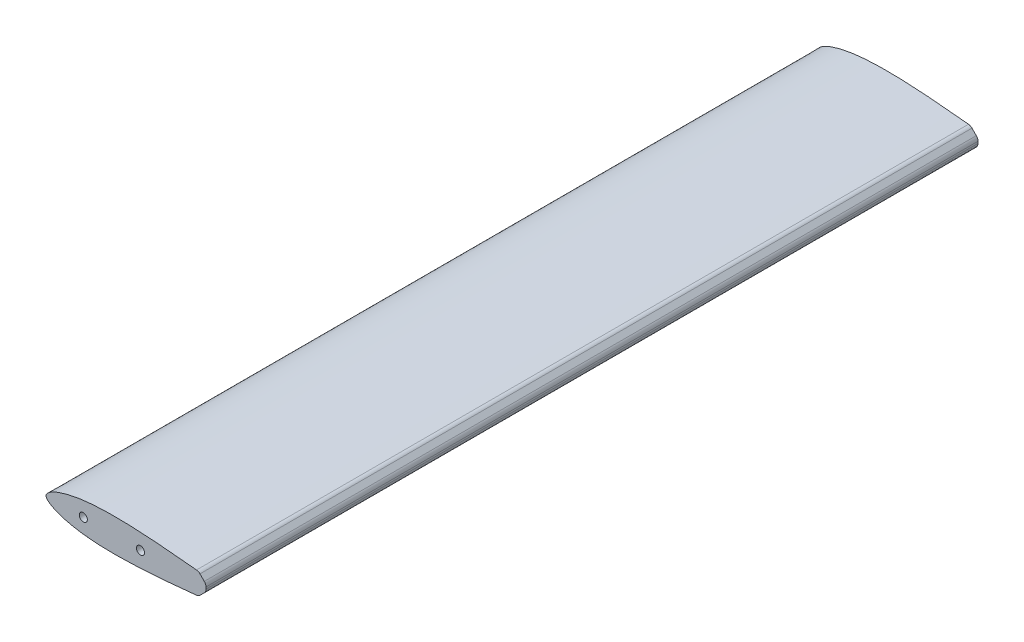
SolidWorks part; units mm, degrees
material "Wing Foam"
ref_plane "Front Plane" through (0, 0, 0) normal (0, 0, 1) x (1, 0, 0)
ref_plane "Top Plane" through (0, 0, 0) normal (0, 1, 0) x (1, 0, 0)
ref_plane "Right Plane" through (0, 0, 0) normal (1, 0, 0) x (0, 0, -1)
curve "Curve2"
  spline degree 3 poles (25.2129, -0.0083, 0) (25.4479, 0, 0) (25.2129, 0.0083, 0) (25.0266, 0.0317, 0) (24.5854, 0.0743, 0) (24.0514, 0.1262, 0) (23.3593, 0.1828, 0) (22.5445, 0.2515, 0) (21.6077, 0.334, 0) (20.5667, 0.4316, 0) (19.4358, 0.5428, 0) (18.232, 0.6656, 0) (16.9723, 0.7976, 0) (15.6739, 0.934, 0) (14.3536, 1.0707, 0) (13.0278, 1.2023, 0) (11.7119, 1.3224, 0) (10.4203, 1.4262, 0) (9.1661, 1.5078, 0) (7.9608, 1.5623, 0) (6.8146, 1.5854, 0) (5.7365, 1.5758, 0) (4.7346, 1.5313, 0) (3.8153, 1.4513, 0) (2.9837, 1.336, 0) (2.2443, 1.1893, 0) (1.6014, 1.0184, 0) (1.0596, 0.829, 0) (0.6236, 0.6287, 0) (0.2959, 0.4198, 0) (0.0819, 0.2242, 0) (-0.0333, 0, 0) (0.0819, -0.2242, 0) (0.2959, -0.4198, 0) (0.6236, -0.6287, 0) (1.0596, -0.829, 0) (1.6014, -1.0184, 0) (2.2443, -1.1893, 0) (2.9837, -1.336, 0) (3.8153, -1.4513, 0) (4.7346, -1.5313, 0) (5.7365, -1.5758, 0) (6.8146, -1.5854, 0) (7.9608, -1.5623, 0) (9.1661, -1.5078, 0) (10.4203, -1.4262, 0) (11.7119, -1.3224, 0) (13.0278, -1.2023, 0) (14.3536, -1.0707, 0) (15.6739, -0.934, 0) (16.9723, -0.7976, 0) (18.232, -0.6656, 0) (19.4358, -0.5428, 0) (20.5667, -0.4316, 0) (21.6077, -0.334, 0) (22.5445, -0.2515, 0) (23.3593, -0.1828, 0) (24.0514, -0.1262, 0) (24.5854, -0.0743, 0) (25.0266, -0.0317, 0) (25.2129, -0.0083, 0) (25.4479, 0, 0) (25.2129, 0.0083, 0) knots -0.014696 -0.00674 -0.001726 0 0.001726 0.00674 0.014696 0.025359 0.038701 0.054619 0.072867 0.093174 0.115236 0.138727 0.163314 0.188652 0.214406 0.240251 0.265875 0.290998 0.315355 0.338723 0.360924 0.381802 0.401202 0.419043 0.435269 0.449839 0.46271 0.473799 0.48306 0.490498 0.496137 0.5 0.503863 0.509502 0.51694 0.526201 0.53729 0.550161 0.564731 0.580957 0.598798 0.618198 0.639076 0.661277 0.684645 0.709002 0.734125 0.759749 0.785594 0.811348 0.836686 0.861273 0.884764 0.906826 0.927133 0.945381 0.961299 0.974641 0.985304 0.99326 0.998274 1 1.001726 1.00674 1.014696 periodic
sketch "Sketch4" plane through (0, 0, 0) normal (0, 0, 1) x (1, 0, 0)
  line L0 (0, 1.7966) -> (0, -1.8631) construction
  line L1 (234.188, 0) -> (0, 0) construction
  spline S2 degree 3 poles (232.4627, -0.0763) (234.6297, 0) (232.4627, 0.0763) (230.7453, 0.2925) (226.6771, 0.6852) (221.7536, 1.164) (215.3729, 1.6852) (207.8606, 2.3193) (199.2232, 3.0796) (189.6249, 3.9791) (179.1985, 5.0042) (168.0995, 6.1368) (156.485, 7.3536) (144.513, 8.6117) (132.34, 9.8717) (120.1165, 11.0852) (107.9836, 12.1928) (96.0751, 13.1495) (84.5114, 13.9023) (73.3989, 14.4043) (62.8304, 14.6175) (52.8907, 14.5289) (43.6527, 14.1188) (35.1769, 13.3807) (27.5098, 12.3176) (20.6924, 10.9653) (14.765, 9.3899) (9.7694, 7.6438) (5.7494, 5.7962) (2.7281, 3.8708) (0.7551, 2.0669) (-0.307, 0) (0.7551, -2.0669) (2.7281, -3.8708) (5.7494, -5.7962) (9.7694, -7.6438) (14.765, -9.3899) (20.6924, -10.9653) (27.5098, -12.3176) (35.1769, -13.3807) (43.6527, -14.1188) (52.8907, -14.5289) (62.8304, -14.6175) (73.3989, -14.4043) (84.5114, -13.9023) (96.0751, -13.1495) (107.9836, -12.1928) (120.1165, -11.0852) (132.34, -9.8717) (144.513, -8.6117) (156.485, -7.3536) (168.0995, -6.1368) (179.1985, -5.0042) (189.6249, -3.9791) (199.2232, -3.0796) (207.8606, -2.3193) (215.3729, -1.6852) (221.7536, -1.164) (226.6771, -0.6852) (230.7453, -0.2925) (232.4627, -0.0763) (234.6297, 0) (232.4627, 0.0763) knots -0.014696 -0.00674 -0.001726 0 0.001726 0.00674 0.014696 0.025359 0.038701 0.054619 0.072867 0.093174 0.115236 0.138727 0.163314 0.188652 0.214406 0.240251 0.265875 0.290998 0.315355 0.338723 0.360924 0.381802 0.401202 0.419043 0.435269 0.449839 0.46271 0.473799 0.48306 0.490498 0.496137 0.5 0.503863 0.509502 0.51694 0.526201 0.53729 0.550161 0.564731 0.580957 0.598798 0.618198 0.639076 0.661277 0.684645 0.709002 0.734125 0.759749 0.785594 0.811348 0.836686 0.861273 0.884764 0.906826 0.927133 0.945381 0.961299 0.974641 0.985304 0.99326 0.998274 1 1.001726 1.00674 1.014696 only from (234.188, 0) to (234.188, 0)
  dimension "D1" = 234.188
extrude "Boss-Extrude1" add sketch "Sketch4" along normal mid plane 685.8
sketch "Sketch5" plane through (0, 0, -342.9) normal (0, 0, -1) x (-1, 0, 0)
  line L0 (0, 0) -> (-230.7877, -0.2744) construction
  circle A0 centre (-33.147, -0.0394) radius 3.6
  circle A1 centre (-83.947, -0.0998) radius 3.6
  spline S0 degree 3 poles (-232.4627, 0.0763) (-234.6297, 0) (-232.4627, -0.0763) (-230.7453, -0.2925) (-226.6771, -0.6852) (-221.7536, -1.164) (-215.3729, -1.6852) (-207.8606, -2.3193) (-199.2232, -3.0796) (-189.6249, -3.9791) (-179.1985, -5.0042) (-168.0995, -6.1368) (-156.485, -7.3536) (-144.513, -8.6117) (-132.34, -9.8717) (-120.1165, -11.0852) (-107.9836, -12.1928) (-96.0751, -13.1495) (-84.5114, -13.9023) (-73.3989, -14.4043) (-62.8304, -14.6175) (-52.8907, -14.5289) (-43.6527, -14.1188) (-35.1769, -13.3807) (-27.5098, -12.3176) (-20.6924, -10.9653) (-14.765, -9.3899) (-9.7694, -7.6438) (-5.7494, -5.7962) (-2.7281, -3.8708) (-0.7551, -2.0669) (0.307, 0) (-0.7551, 2.0669) (-2.7281, 3.8708) (-5.7494, 5.7962) (-9.7694, 7.6438) (-14.765, 9.3899) (-20.6924, 10.9653) (-27.5098, 12.3176) (-35.1769, 13.3807) (-43.6527, 14.1188) (-52.8907, 14.5289) (-62.8304, 14.6175) (-73.3989, 14.4043) (-84.5114, 13.9023) (-96.0751, 13.1495) (-107.9836, 12.1928) (-120.1165, 11.0852) (-132.34, 9.8717) (-144.513, 8.6117) (-156.485, 7.3536) (-168.0995, 6.1368) (-179.1985, 5.0042) (-189.6249, 3.9791) (-199.2232, 3.0796) (-207.8606, 2.3193) (-215.3729, 1.6852) (-221.7536, 1.164) (-226.6771, 0.6852) (-230.7453, 0.2925) (-232.4627, 0.0763) (-234.6297, 0) (-232.4627, -0.0763) knots -0.014696 -0.00674 -0.001726 0 0.001726 0.00674 0.014696 0.025359 0.038701 0.054619 0.072867 0.093174 0.115236 0.138727 0.163314 0.188652 0.214406 0.240251 0.265875 0.290998 0.315355 0.338723 0.360924 0.381802 0.401202 0.419043 0.435269 0.449839 0.46271 0.473799 0.48306 0.490498 0.496137 0.5 0.503863 0.509502 0.51694 0.526201 0.53729 0.550161 0.564731 0.580957 0.598798 0.618198 0.639076 0.661277 0.684645 0.709002 0.734125 0.759749 0.785594 0.811348 0.836686 0.861273 0.884764 0.906826 0.927133 0.945381 0.961299 0.974641 0.985304 0.99326 0.998274 1 1.001726 1.00674 1.014696 only from (-234.188, 0) to (-234.188, 0) construction
  dimension "D1" = 7.2
  dimension "D2" = 33.147
  dimension "D3" = 50.8
extrude "Cut-Extrude1" cut sketch "Sketch5" against normal up to next
sketch "Sketch6" plane through (0, 0, 342.9) normal (0, 0, 1) x (1, 0, 0)
  line L0 (142.113, -8.8584) -> (142.113, 8.8584)
  line L1 (135.485, -9.5426) -> (142.113, -2.9146)
  line L2 (142.113, -2.9146) -> (147.4954, -8.297)
  line L3 (135.5041, 9.5406) -> (142.113, 2.9318)
  line L4 (142.113, 2.9318) -> (147.4798, 8.2986)
  spline S0 degree 3 poles (232.4627, -0.0763) (234.6297, 0) (232.4627, 0.0763) (230.7453, 0.2925) (226.6771, 0.6852) (221.7536, 1.164) (215.3729, 1.6852) (207.8606, 2.3193) (199.2232, 3.0796) (189.6249, 3.9791) (179.1985, 5.0042) (168.0995, 6.1368) (156.485, 7.3536) (144.513, 8.6117) (132.34, 9.8717) (120.1165, 11.0852) (107.9836, 12.1928) (96.0751, 13.1495) (84.5114, 13.9023) (73.3989, 14.4043) (62.8304, 14.6175) (52.8907, 14.5289) (43.6527, 14.1188) (35.1769, 13.3807) (27.5098, 12.3176) (20.6924, 10.9653) (14.765, 9.3899) (9.7694, 7.6438) (5.7494, 5.7962) (2.7281, 3.8708) (0.7551, 2.0669) (-0.307, 0) (0.7551, -2.0669) (2.7281, -3.8708) (5.7494, -5.7962) (9.7694, -7.6438) (14.765, -9.3899) (20.6924, -10.9653) (27.5098, -12.3176) (35.1769, -13.3807) (43.6527, -14.1188) (52.8907, -14.5289) (62.8304, -14.6175) (73.3989, -14.4043) (84.5114, -13.9023) (96.0751, -13.1495) (107.9836, -12.1928) (120.1165, -11.0852) (132.34, -9.8717) (144.513, -8.6117) (156.485, -7.3536) (168.0995, -6.1368) (179.1985, -5.0042) (189.6249, -3.9791) (199.2232, -3.0796) (207.8606, -2.3193) (215.3729, -1.6852) (221.7536, -1.164) (226.6771, -0.6852) (230.7453, -0.2925) (232.4627, -0.0763) (234.6297, 0) (232.4627, 0.0763) knots -0.014696 -0.00674 -0.001726 0 0.001726 0.00674 0.014696 0.025359 0.038701 0.054619 0.072867 0.093174 0.115236 0.138727 0.163314 0.188652 0.214406 0.240251 0.265875 0.290998 0.315355 0.338723 0.360924 0.381802 0.401202 0.419043 0.435269 0.449839 0.46271 0.473799 0.48306 0.490498 0.496137 0.5 0.503863 0.509502 0.51694 0.526201 0.53729 0.550161 0.564731 0.580957 0.598798 0.618198 0.639076 0.661277 0.684645 0.709002 0.734125 0.759749 0.785594 0.811348 0.836686 0.861273 0.884764 0.906826 0.927133 0.945381 0.961299 0.974641 0.985304 0.99326 0.998274 1 1.001726 1.00674 1.014696 only from (234.188, 0) to (234.188, 0) construction
  spline S1 degree 3 poles (232.4627, -0.0763) (234.6297, 0) (232.4627, 0.0763) (230.7453, 0.2925) (226.6771, 0.6852) (221.7536, 1.164) (215.3729, 1.6852) (207.8606, 2.3193) (199.2232, 3.0796) (189.6249, 3.9791) (179.1985, 5.0042) (168.0995, 6.1368) (156.485, 7.3536) (144.513, 8.6117) (132.34, 9.8717) (120.1165, 11.0852) (107.9836, 12.1928) (96.0751, 13.1495) (84.5114, 13.9023) (73.3989, 14.4043) (62.8304, 14.6175) (52.8907, 14.5289) (43.6527, 14.1188) (35.1769, 13.3807) (27.5098, 12.3176) (20.6924, 10.9653) (14.765, 9.3899) (9.7694, 7.6438) (5.7494, 5.7962) (2.7281, 3.8708) (0.7551, 2.0669) (-0.307, 0) (0.7551, -2.0669) (2.7281, -3.8708) (5.7494, -5.7962) (9.7694, -7.6438) (14.765, -9.3899) (20.6924, -10.9653) (27.5098, -12.3176) (35.1769, -13.3807) (43.6527, -14.1188) (52.8907, -14.5289) (62.8304, -14.6175) (73.3989, -14.4043) (84.5114, -13.9023) (96.0751, -13.1495) (107.9836, -12.1928) (120.1165, -11.0852) (132.34, -9.8717) (144.513, -8.6117) (156.485, -7.3536) (168.0995, -6.1368) (179.1985, -5.0042) (189.6249, -3.9791) (199.2232, -3.0796) (207.8606, -2.3193) (215.3729, -1.6852) (221.7536, -1.164) (226.6771, -0.6852) (230.7453, -0.2925) (232.4627, -0.0763) (234.6297, 0) (232.4627, 0.0763) knots -0.014696 -0.00674 -0.001726 0 0.001726 0.00674 0.014696 0.025359 0.038701 0.054619 0.072867 0.093174 0.115236 0.138727 0.163314 0.188652 0.214406 0.240251 0.265875 0.290998 0.315355 0.338723 0.360924 0.381802 0.401202 0.419043 0.435269 0.449839 0.46271 0.473799 0.48306 0.490498 0.496137 0.5 0.503863 0.509502 0.51694 0.526201 0.53729 0.550161 0.564731 0.580957 0.598798 0.618198 0.639076 0.661277 0.684645 0.709002 0.734125 0.759749 0.785594 0.811348 0.836686 0.861273 0.884764 0.906826 0.927133 0.945381 0.961299 0.974641 0.985304 0.99326 0.998274 1 1.001726 1.00674 1.014696 only from (234.188, 0) to (234.188, 0)
  point P3 (234.188, 0)
  spline M9 degree 3 poles (232.4627, -0.0763) (234.6297, 0) (232.4627, 0.0763) (230.7453, 0.2925) (226.6771, 0.6852) (221.7536, 1.164) (215.3729, 1.6852) (207.8606, 2.3193) (199.2232, 3.0796) (189.6249, 3.9791) (179.1985, 5.0042) (168.0995, 6.1368) (156.485, 7.3536) (144.513, 8.6117) (132.34, 9.8717) (120.1165, 11.0852) (107.9836, 12.1928) (96.0751, 13.1495) (84.5114, 13.9023) (73.3989, 14.4043) (62.8304, 14.6175) (52.8907, 14.5289) (43.6527, 14.1188) (35.1769, 13.3807) (27.5098, 12.3176) (20.6924, 10.9653) (14.765, 9.3899) (9.7694, 7.6438) (5.7494, 5.7962) (2.7281, 3.8708) (0.7551, 2.0669) (-0.307, 0) (0.7551, -2.0669) (2.7281, -3.8708) (5.7494, -5.7962) (9.7694, -7.6438) (14.765, -9.3899) (20.6924, -10.9653) (27.5098, -12.3176) (35.1769, -13.3807) (43.6527, -14.1188) (52.8907, -14.5289) (62.8304, -14.6175) (73.3989, -14.4043) (84.5114, -13.9023) (96.0751, -13.1495) (107.9836, -12.1928) (120.1165, -11.0852) (132.34, -9.8717) (144.513, -8.6117) (156.485, -7.3536) (168.0995, -6.1368) (179.1985, -5.0042) (189.6249, -3.9791) (199.2232, -3.0796) (207.8606, -2.3193) (215.3729, -1.6852) (221.7536, -1.164) (226.6771, -0.6852) (230.7453, -0.2925) (232.4627, -0.0763) (234.6297, 0) (232.4627, 0.0763) knots -0.014696 -0.00674 -0.001726 0 0.001726 0.00674 0.014696 0.025359 0.038701 0.054619 0.072867 0.093174 0.115236 0.138727 0.163314 0.188652 0.214406 0.240251 0.265875 0.290998 0.315355 0.338723 0.360924 0.381802 0.401202 0.419043 0.435269 0.449839 0.46271 0.473799 0.48306 0.490498 0.496137 0.5 0.503863 0.509502 0.51694 0.526201 0.53729 0.550161 0.564731 0.580957 0.598798 0.618198 0.639076 0.661277 0.684645 0.709002 0.734125 0.759749 0.785594 0.811348 0.836686 0.861273 0.884764 0.906826 0.927133 0.945381 0.961299 0.974641 0.985304 0.99326 0.998274 1 1.001726 1.00674 1.014696
  dimension "D1" = 92.075
  dimension "D2" = 11.773
  dimension "D3" = 5.9267
  dimension "D4" = 45
  dimension "D5" = 45
  dimension "D6" = 45
  dimension "D7" = 45
extrude "Cut-Extrude2" cut sketch "Sketch6" against normal through all contours L4 L0 L2 M9 | L2 L0 M9 | L1 L0 M9 | L3 L0 M9 | L0 L4 M9 region at (139.9033, -7.1058, 342.9) region at (143.9072, -6.6902, 342.9) region at (173.4284, 0.0007, 342.9) region at (139.9097, 7.1109, 342.9) region at (143.902, 6.6965, 342.9)
fillet "Fillet1" radius 5.08 4 edges at (135.5041, 9.5406, 0) (142.113, 2.9318, 0) (142.113, -2.9146, 0) (135.485, -9.5426, 0)
ref_axis "Axis1" through (142.113, 0.0086, -342.9) along (0, 0, 1)
equation "\"SA\"= 27 * \"CHORD\"'Meters Squared to In Squared"
equation "\"CHORD\"= 9.22"
equation "\"L\"= 27"
equation "\"D1@Sketch4\"=\"CHORD\""
equation "\"D1@Boss-Extrude1\"=\"L\""
equation "\"D2@Sketch5\"=\"CHORD\"/4-1"
equation "\"AR\"= 2.9"
